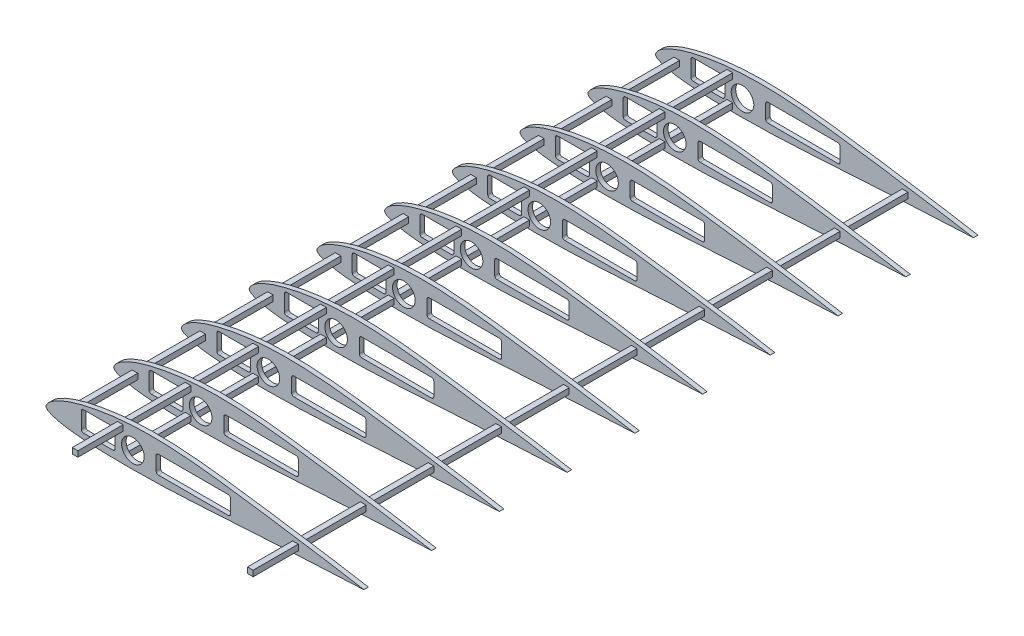
SolidWorks part; units mm, degrees
ref_plane "Front Plane" through (0, 0, 0) normal (0, 0, 1) x (1, 0, 0)
ref_plane "Top Plane" through (0, 0, 0) normal (0, 1, 0) x (1, 0, 0)
ref_plane "Right Plane" through (0, 0, 0) normal (1, 0, 0) x (0, 0, -1)
curve "Curve1"
  spline degree 3 poles (25.2088, 0.0031, 0) (25.4484, -0.0031, 0) (25.2117, 0.0209, 0) (25.0251, 0.0571, 0) (24.5852, 0.1328, 0) (24.06, 0.2322, 0) (23.3873, 0.3478, 0) (22.6018, 0.4739, 0) (21.7032, 0.6151, 0) (20.7068, 0.7694, 0) (19.6256, 0.9351, 0) (18.475, 1.1087, 0) (17.2708, 1.2865, 0) (16.0292, 1.4651, 0) (14.7666, 1.6379, 0) (13.5001, 1.8004, 0) (12.2446, 1.9439, 0) (11.0116, 2.0561, 0) (9.8099, 2.1301, 0) (8.6464, 2.1619, 0) (7.5276, 2.1493, 0) (6.459, 2.093, 0) (5.4467, 1.9949, 0) (4.4976, 1.8641, 0) (3.6202, 1.7053, 0) (2.8233, 1.523, 0) (2.1144, 1.3219, 0) (1.5008, 1.1059, 0) (0.9865, 0.8803, 0) (0.5779, 0.652, 0) (0.2708, 0.4245, 0) (0.0836, 0.2161, 0) (-0.0349, 0.004, 0) (0.089, -0.2027, 0) (0.3409, -0.3252, 0) (0.701, -0.4662, 0) (1.1913, -0.581, 0) (1.8002, -0.6841, 0) (2.5267, -0.768, 0) (3.3632, -0.8336, 0) (4.3022, -0.8807, 0) (5.334, -0.9092, 0) (6.4474, -0.9203, 0) (7.6302, -0.9134, 0) (8.8703, -0.8889, 0) (10.1572, -0.841, 0) (11.4808, -0.7741, 0) (12.8288, -0.6974, 0) (14.1854, -0.6164, 0) (15.5332, -0.5343, 0) (16.8545, -0.4545, 0) (18.1325, -0.3787, 0) (19.3501, -0.3089, 0) (20.4916, -0.2458, 0) (21.5411, -0.1904, 0) (22.4855, -0.1429, 0) (23.3092, -0.1017, 0) (24.0133, -0.0644, 0) (24.5612, -0.0287, 0) (25.0167, -0.0091, 0) (25.2088, 0.0031, 0) (25.4484, -0.0031, 0) (25.2117, 0.0209, 0) knots -0.015092 -0.006889 -0.001754 0 0.001748 0.006827 0.01488 0.025572 0.038694 0.054171 0.071834 0.091435 0.112685 0.135293 0.158944 0.183315 0.20807 0.232879 0.257399 0.281384 0.304706 0.327241 0.348897 0.369607 0.389308 0.407886 0.425177 0.441027 0.4553 0.467904 0.478752 0.487814 0.49509 0.500617 0.504451 0.507804 0.513091 0.520546 0.530249 0.542214 0.556382 0.572656 0.590895 0.610925 0.632536 0.655496 0.679547 0.704499 0.730211 0.756436 0.782837 0.809062 0.834776 0.859641 0.883338 0.905541 0.925965 0.944326 0.960366 0.973929 0.984908 0.993111 0.998246 1 1.001748 1.006827 1.01488 periodic
sketch "Sketch1" plane through (0, 0, 0) normal (0, 0, 1) x (1, 0, 0)
  line L0 (357.6496, 0) -> (0, 0) construction
  line L1 (0, 0) -> (0, 5.0209) construction
  spline S1 degree 3 poles (354.9573, 0.0431) (358.3317, -0.0432) (354.9981, 0.2938) (352.3707, 0.8024) (346.1763, 1.8676) (338.7813, 3.2655) (329.3081, 4.8919) (318.2482, 6.6648) (305.5952, 8.6507) (291.564, 10.8193) (276.34, 13.1505) (260.1392, 15.5903) (243.1815, 18.0913) (225.699, 20.6027) (207.9209, 23.0318) (190.087, 25.3152) (172.4086, 27.3328) (155.0467, 28.9096) (138.1258, 29.947) (121.7437, 30.3922) (105.9899, 30.2108) (90.9433, 29.4155) (76.6903, 28.0308) (63.3272, 26.1868) (50.9728, 23.9485) (39.7523, 21.3791) (29.7714, 18.545) (21.1318, 15.5018) (13.8914, 12.3237) (8.1391, 9.1075) (3.8158, 5.9031) (1.1802, 2.9693) (-0.4877, -0.018) (1.2572, -2.9285) (4.805, -4.6528) (9.8754, -6.6365) (16.78, -8.2511) (25.3535, -9.7017) (35.5828, -10.8813) (47.3622, -11.8027) (60.5842, -12.4624) (75.1117, -12.8607) (90.7897, -13.0132) (107.4435, -12.9137) (124.9052, -12.5651) (143.0256, -11.8868) (161.6617, -10.9405) (180.6424, -9.8572) (199.7442, -8.7119) (218.721, -7.5525) (237.3263, -6.4253) (255.3201, -5.3536) (272.4652, -4.367) (288.5372, -3.4753) (303.3148, -2.6922) (316.6121, -2.0207) (328.2104, -1.4385) (338.1246, -0.9102) (345.8395, -0.4061) (352.2525, -0.129) (354.9573, 0.0431) (358.3317, -0.0432) (354.9981, 0.2938) knots -0.015092 -0.006889 -0.001754 0 0.001748 0.006827 0.01488 0.025572 0.038694 0.054171 0.071834 0.091435 0.112685 0.135293 0.158944 0.183315 0.20807 0.232879 0.257399 0.281384 0.304706 0.327241 0.348897 0.369607 0.389308 0.407886 0.425177 0.441027 0.4553 0.467904 0.478752 0.487814 0.49509 0.500617 0.504451 0.507804 0.513091 0.520546 0.530249 0.542214 0.556382 0.572656 0.590895 0.610925 0.632536 0.655496 0.679547 0.704499 0.730211 0.756436 0.782837 0.809062 0.834776 0.859641 0.883338 0.905541 0.925965 0.944326 0.960366 0.973929 0.984908 0.993111 0.998246 1 1.001748 1.006827 1.01488 only from (357.6496, 0) to (357.6496, 0)
  dimension "D1" = 357.6496
ref_plane "Plane3" through (0, 0, 76.2) normal (0, 0, 1) x (1, 0, 0)
ref_plane "Plane4" through (0, 0, 152.4) normal (0, 0, 1) x (1, 0, 0)
ref_plane "Plane5" through (0, 0, 228.6) normal (0, 0, 1) x (1, 0, 0)
ref_plane "Plane6" through (0, 0, 304.8) normal (0, 0, 1) x (1, 0, 0)
ref_plane "Plane7" through (0, 0, 381) normal (0, 0, 1) x (1, 0, 0)
ref_plane "Plane8" through (0, 0, 457.2) normal (0, 0, 1) x (1, 0, 0)
ref_plane "Plane9" through (0, 0, 533.4) normal (0, 0, 1) x (1, 0, 0)
ref_plane "Plane10" through (0, 0, 609.6) normal (0, 0, 1) x (1, 0, 0)
ref_plane "Plane11" through (0, 0, 685.8) normal (0, 0, 1) x (1, 0, 0)
sketch "Sketch5" plane through (0, 0, 76.2) normal (0, 0, 1) x (1, 0, 0)
  spline S0 degree 3 poles (354.9573, 0.0431) (358.3317, -0.0432) (354.9981, 0.2938) (352.3707, 0.8024) (346.1763, 1.8676) (338.7813, 3.2655) (329.3081, 4.8919) (318.2482, 6.6648) (305.5952, 8.6507) (291.564, 10.8193) (276.34, 13.1505) (260.1392, 15.5903) (243.1815, 18.0913) (225.699, 20.6027) (207.9209, 23.0318) (190.087, 25.3152) (172.4086, 27.3328) (155.0467, 28.9096) (138.1258, 29.947) (121.7437, 30.3922) (105.9899, 30.2108) (90.9433, 29.4155) (76.6903, 28.0308) (63.3272, 26.1868) (50.9728, 23.9485) (39.7523, 21.3791) (29.7714, 18.545) (21.1318, 15.5018) (13.8914, 12.3237) (8.1391, 9.1075) (3.8158, 5.9031) (1.1802, 2.9693) (-0.4877, -0.018) (1.2572, -2.9285) (4.805, -4.6528) (9.8754, -6.6365) (16.78, -8.2511) (25.3535, -9.7017) (35.5828, -10.8813) (47.3622, -11.8027) (60.5842, -12.4624) (75.1117, -12.8607) (90.7897, -13.0132) (107.4435, -12.9137) (124.9052, -12.5651) (143.0256, -11.8868) (161.6617, -10.9405) (180.6424, -9.8572) (199.7442, -8.7119) (218.721, -7.5525) (237.3263, -6.4253) (255.3201, -5.3536) (272.4652, -4.367) (288.5372, -3.4753) (303.3148, -2.6922) (316.6121, -2.0207) (328.2104, -1.4385) (338.1246, -0.9102) (345.8395, -0.4061) (352.2525, -0.129) (354.9573, 0.0431) (358.3317, -0.0432) (354.9981, 0.2938) knots -0.015092 -0.006889 -0.001754 0 0.001748 0.006827 0.01488 0.025572 0.038694 0.054171 0.071834 0.091435 0.112685 0.135293 0.158944 0.183315 0.20807 0.232879 0.257399 0.281384 0.304706 0.327241 0.348897 0.369607 0.389308 0.407886 0.425177 0.441027 0.4553 0.467904 0.478752 0.487814 0.49509 0.500617 0.504451 0.507804 0.513091 0.520546 0.530249 0.542214 0.556382 0.572656 0.590895 0.610925 0.632536 0.655496 0.679547 0.704499 0.730211 0.756436 0.782837 0.809062 0.834776 0.859641 0.883338 0.905541 0.925965 0.944326 0.960366 0.973929 0.984908 0.993111 0.998246 1 1.001748 1.006827 1.01488 only from (357.6496, 0) to (357.6496, 0) construction
  spline S1 degree 3 poles (354.9573, 0.0431) (358.3317, -0.0432) (354.9981, 0.2938) (352.3707, 0.8024) (346.1763, 1.8676) (338.7813, 3.2655) (329.3081, 4.8919) (318.2482, 6.6648) (305.5952, 8.6507) (291.564, 10.8193) (276.34, 13.1505) (260.1392, 15.5903) (243.1815, 18.0913) (225.699, 20.6027) (207.9209, 23.0318) (190.087, 25.3152) (172.4086, 27.3328) (155.0467, 28.9096) (138.1258, 29.947) (121.7437, 30.3922) (105.9899, 30.2108) (90.9433, 29.4155) (76.6903, 28.0308) (63.3272, 26.1868) (50.9728, 23.9485) (39.7523, 21.3791) (29.7714, 18.545) (21.1318, 15.5018) (13.8914, 12.3237) (8.1391, 9.1075) (3.8158, 5.9031) (1.1802, 2.9693) (-0.4877, -0.018) (1.2572, -2.9285) (4.805, -4.6528) (9.8754, -6.6365) (16.78, -8.2511) (25.3535, -9.7017) (35.5828, -10.8813) (47.3622, -11.8027) (60.5842, -12.4624) (75.1117, -12.8607) (90.7897, -13.0132) (107.4435, -12.9137) (124.9052, -12.5651) (143.0256, -11.8868) (161.6617, -10.9405) (180.6424, -9.8572) (199.7442, -8.7119) (218.721, -7.5525) (237.3263, -6.4253) (255.3201, -5.3536) (272.4652, -4.367) (288.5372, -3.4753) (303.3148, -2.6922) (316.6121, -2.0207) (328.2104, -1.4385) (338.1246, -0.9102) (345.8395, -0.4061) (352.2525, -0.129) (354.9573, 0.0431) (358.3317, -0.0432) (354.9981, 0.2938) knots -0.015092 -0.006889 -0.001754 0 0.001748 0.006827 0.01488 0.025572 0.038694 0.054171 0.071834 0.091435 0.112685 0.135293 0.158944 0.183315 0.20807 0.232879 0.257399 0.281384 0.304706 0.327241 0.348897 0.369607 0.389308 0.407886 0.425177 0.441027 0.4553 0.467904 0.478752 0.487814 0.49509 0.500617 0.504451 0.507804 0.513091 0.520546 0.530249 0.542214 0.556382 0.572656 0.590895 0.610925 0.632536 0.655496 0.679547 0.704499 0.730211 0.756436 0.782837 0.809062 0.834776 0.859641 0.883338 0.905541 0.925965 0.944326 0.960366 0.973929 0.984908 0.993111 0.998246 1 1.001748 1.006827 1.01488 only from (357.6496, 0) to (357.6496, 0)
sketch "Sketch6" plane through (0, 0, 152.4) normal (0, 0, 1) x (1, 0, 0)
  spline S0 degree 3 poles (354.9573, 0.0431) (358.3317, -0.0432) (354.9981, 0.2938) (352.3707, 0.8024) (346.1763, 1.8676) (338.7813, 3.2655) (329.3081, 4.8919) (318.2482, 6.6648) (305.5952, 8.6507) (291.564, 10.8193) (276.34, 13.1505) (260.1392, 15.5903) (243.1815, 18.0913) (225.699, 20.6027) (207.9209, 23.0318) (190.087, 25.3152) (172.4086, 27.3328) (155.0467, 28.9096) (138.1258, 29.947) (121.7437, 30.3922) (105.9899, 30.2108) (90.9433, 29.4155) (76.6903, 28.0308) (63.3272, 26.1868) (50.9728, 23.9485) (39.7523, 21.3791) (29.7714, 18.545) (21.1318, 15.5018) (13.8914, 12.3237) (8.1391, 9.1075) (3.8158, 5.9031) (1.1802, 2.9693) (-0.4877, -0.018) (1.2572, -2.9285) (4.805, -4.6528) (9.8754, -6.6365) (16.78, -8.2511) (25.3535, -9.7017) (35.5828, -10.8813) (47.3622, -11.8027) (60.5842, -12.4624) (75.1117, -12.8607) (90.7897, -13.0132) (107.4435, -12.9137) (124.9052, -12.5651) (143.0256, -11.8868) (161.6617, -10.9405) (180.6424, -9.8572) (199.7442, -8.7119) (218.721, -7.5525) (237.3263, -6.4253) (255.3201, -5.3536) (272.4652, -4.367) (288.5372, -3.4753) (303.3148, -2.6922) (316.6121, -2.0207) (328.2104, -1.4385) (338.1246, -0.9102) (345.8395, -0.4061) (352.2525, -0.129) (354.9573, 0.0431) (358.3317, -0.0432) (354.9981, 0.2938) knots -0.015092 -0.006889 -0.001754 0 0.001748 0.006827 0.01488 0.025572 0.038694 0.054171 0.071834 0.091435 0.112685 0.135293 0.158944 0.183315 0.20807 0.232879 0.257399 0.281384 0.304706 0.327241 0.348897 0.369607 0.389308 0.407886 0.425177 0.441027 0.4553 0.467904 0.478752 0.487814 0.49509 0.500617 0.504451 0.507804 0.513091 0.520546 0.530249 0.542214 0.556382 0.572656 0.590895 0.610925 0.632536 0.655496 0.679547 0.704499 0.730211 0.756436 0.782837 0.809062 0.834776 0.859641 0.883338 0.905541 0.925965 0.944326 0.960366 0.973929 0.984908 0.993111 0.998246 1 1.001748 1.006827 1.01488 only from (357.6496, 0) to (357.6496, 0) construction
  spline S1 degree 3 poles (354.9573, 0.0431) (358.3317, -0.0432) (354.9981, 0.2938) (352.3707, 0.8024) (346.1763, 1.8676) (338.7813, 3.2655) (329.3081, 4.8919) (318.2482, 6.6648) (305.5952, 8.6507) (291.564, 10.8193) (276.34, 13.1505) (260.1392, 15.5903) (243.1815, 18.0913) (225.699, 20.6027) (207.9209, 23.0318) (190.087, 25.3152) (172.4086, 27.3328) (155.0467, 28.9096) (138.1258, 29.947) (121.7437, 30.3922) (105.9899, 30.2108) (90.9433, 29.4155) (76.6903, 28.0308) (63.3272, 26.1868) (50.9728, 23.9485) (39.7523, 21.3791) (29.7714, 18.545) (21.1318, 15.5018) (13.8914, 12.3237) (8.1391, 9.1075) (3.8158, 5.9031) (1.1802, 2.9693) (-0.4877, -0.018) (1.2572, -2.9285) (4.805, -4.6528) (9.8754, -6.6365) (16.78, -8.2511) (25.3535, -9.7017) (35.5828, -10.8813) (47.3622, -11.8027) (60.5842, -12.4624) (75.1117, -12.8607) (90.7897, -13.0132) (107.4435, -12.9137) (124.9052, -12.5651) (143.0256, -11.8868) (161.6617, -10.9405) (180.6424, -9.8572) (199.7442, -8.7119) (218.721, -7.5525) (237.3263, -6.4253) (255.3201, -5.3536) (272.4652, -4.367) (288.5372, -3.4753) (303.3148, -2.6922) (316.6121, -2.0207) (328.2104, -1.4385) (338.1246, -0.9102) (345.8395, -0.4061) (352.2525, -0.129) (354.9573, 0.0431) (358.3317, -0.0432) (354.9981, 0.2938) knots -0.015092 -0.006889 -0.001754 0 0.001748 0.006827 0.01488 0.025572 0.038694 0.054171 0.071834 0.091435 0.112685 0.135293 0.158944 0.183315 0.20807 0.232879 0.257399 0.281384 0.304706 0.327241 0.348897 0.369607 0.389308 0.407886 0.425177 0.441027 0.4553 0.467904 0.478752 0.487814 0.49509 0.500617 0.504451 0.507804 0.513091 0.520546 0.530249 0.542214 0.556382 0.572656 0.590895 0.610925 0.632536 0.655496 0.679547 0.704499 0.730211 0.756436 0.782837 0.809062 0.834776 0.859641 0.883338 0.905541 0.925965 0.944326 0.960366 0.973929 0.984908 0.993111 0.998246 1 1.001748 1.006827 1.01488 only from (357.6496, 0) to (357.6496, 0)
sketch "Sketch7" plane through (0, 0, 228.6) normal (0, 0, 1) x (1, 0, 0)
  spline S0 degree 3 poles (354.9573, 0.0431) (358.3317, -0.0432) (354.9981, 0.2938) (352.3707, 0.8024) (346.1763, 1.8676) (338.7813, 3.2655) (329.3081, 4.8919) (318.2482, 6.6648) (305.5952, 8.6507) (291.564, 10.8193) (276.34, 13.1505) (260.1392, 15.5903) (243.1815, 18.0913) (225.699, 20.6027) (207.9209, 23.0318) (190.087, 25.3152) (172.4086, 27.3328) (155.0467, 28.9096) (138.1258, 29.947) (121.7437, 30.3922) (105.9899, 30.2108) (90.9433, 29.4155) (76.6903, 28.0308) (63.3272, 26.1868) (50.9728, 23.9485) (39.7523, 21.3791) (29.7714, 18.545) (21.1318, 15.5018) (13.8914, 12.3237) (8.1391, 9.1075) (3.8158, 5.9031) (1.1802, 2.9693) (-0.4877, -0.018) (1.2572, -2.9285) (4.805, -4.6528) (9.8754, -6.6365) (16.78, -8.2511) (25.3535, -9.7017) (35.5828, -10.8813) (47.3622, -11.8027) (60.5842, -12.4624) (75.1117, -12.8607) (90.7897, -13.0132) (107.4435, -12.9137) (124.9052, -12.5651) (143.0256, -11.8868) (161.6617, -10.9405) (180.6424, -9.8572) (199.7442, -8.7119) (218.721, -7.5525) (237.3263, -6.4253) (255.3201, -5.3536) (272.4652, -4.367) (288.5372, -3.4753) (303.3148, -2.6922) (316.6121, -2.0207) (328.2104, -1.4385) (338.1246, -0.9102) (345.8395, -0.4061) (352.2525, -0.129) (354.9573, 0.0431) (358.3317, -0.0432) (354.9981, 0.2938) knots -0.015092 -0.006889 -0.001754 0 0.001748 0.006827 0.01488 0.025572 0.038694 0.054171 0.071834 0.091435 0.112685 0.135293 0.158944 0.183315 0.20807 0.232879 0.257399 0.281384 0.304706 0.327241 0.348897 0.369607 0.389308 0.407886 0.425177 0.441027 0.4553 0.467904 0.478752 0.487814 0.49509 0.500617 0.504451 0.507804 0.513091 0.520546 0.530249 0.542214 0.556382 0.572656 0.590895 0.610925 0.632536 0.655496 0.679547 0.704499 0.730211 0.756436 0.782837 0.809062 0.834776 0.859641 0.883338 0.905541 0.925965 0.944326 0.960366 0.973929 0.984908 0.993111 0.998246 1 1.001748 1.006827 1.01488 only from (357.6496, 0) to (357.6496, 0) construction
  spline S1 degree 3 poles (354.9573, 0.0431) (358.3317, -0.0432) (354.9981, 0.2938) (352.3707, 0.8024) (346.1763, 1.8676) (338.7813, 3.2655) (329.3081, 4.8919) (318.2482, 6.6648) (305.5952, 8.6507) (291.564, 10.8193) (276.34, 13.1505) (260.1392, 15.5903) (243.1815, 18.0913) (225.699, 20.6027) (207.9209, 23.0318) (190.087, 25.3152) (172.4086, 27.3328) (155.0467, 28.9096) (138.1258, 29.947) (121.7437, 30.3922) (105.9899, 30.2108) (90.9433, 29.4155) (76.6903, 28.0308) (63.3272, 26.1868) (50.9728, 23.9485) (39.7523, 21.3791) (29.7714, 18.545) (21.1318, 15.5018) (13.8914, 12.3237) (8.1391, 9.1075) (3.8158, 5.9031) (1.1802, 2.9693) (-0.4877, -0.018) (1.2572, -2.9285) (4.805, -4.6528) (9.8754, -6.6365) (16.78, -8.2511) (25.3535, -9.7017) (35.5828, -10.8813) (47.3622, -11.8027) (60.5842, -12.4624) (75.1117, -12.8607) (90.7897, -13.0132) (107.4435, -12.9137) (124.9052, -12.5651) (143.0256, -11.8868) (161.6617, -10.9405) (180.6424, -9.8572) (199.7442, -8.7119) (218.721, -7.5525) (237.3263, -6.4253) (255.3201, -5.3536) (272.4652, -4.367) (288.5372, -3.4753) (303.3148, -2.6922) (316.6121, -2.0207) (328.2104, -1.4385) (338.1246, -0.9102) (345.8395, -0.4061) (352.2525, -0.129) (354.9573, 0.0431) (358.3317, -0.0432) (354.9981, 0.2938) knots -0.015092 -0.006889 -0.001754 0 0.001748 0.006827 0.01488 0.025572 0.038694 0.054171 0.071834 0.091435 0.112685 0.135293 0.158944 0.183315 0.20807 0.232879 0.257399 0.281384 0.304706 0.327241 0.348897 0.369607 0.389308 0.407886 0.425177 0.441027 0.4553 0.467904 0.478752 0.487814 0.49509 0.500617 0.504451 0.507804 0.513091 0.520546 0.530249 0.542214 0.556382 0.572656 0.590895 0.610925 0.632536 0.655496 0.679547 0.704499 0.730211 0.756436 0.782837 0.809062 0.834776 0.859641 0.883338 0.905541 0.925965 0.944326 0.960366 0.973929 0.984908 0.993111 0.998246 1 1.001748 1.006827 1.01488 only from (357.6496, 0) to (357.6496, 0)
sketch "Sketch8" plane through (0, 0, 304.8) normal (0, 0, 1) x (1, 0, 0)
  spline S0 degree 3 poles (354.9573, 0.0431) (358.3317, -0.0432) (354.9981, 0.2938) (352.3707, 0.8024) (346.1763, 1.8676) (338.7813, 3.2655) (329.3081, 4.8919) (318.2482, 6.6648) (305.5952, 8.6507) (291.564, 10.8193) (276.34, 13.1505) (260.1392, 15.5903) (243.1815, 18.0913) (225.699, 20.6027) (207.9209, 23.0318) (190.087, 25.3152) (172.4086, 27.3328) (155.0467, 28.9096) (138.1258, 29.947) (121.7437, 30.3922) (105.9899, 30.2108) (90.9433, 29.4155) (76.6903, 28.0308) (63.3272, 26.1868) (50.9728, 23.9485) (39.7523, 21.3791) (29.7714, 18.545) (21.1318, 15.5018) (13.8914, 12.3237) (8.1391, 9.1075) (3.8158, 5.9031) (1.1802, 2.9693) (-0.4877, -0.018) (1.2572, -2.9285) (4.805, -4.6528) (9.8754, -6.6365) (16.78, -8.2511) (25.3535, -9.7017) (35.5828, -10.8813) (47.3622, -11.8027) (60.5842, -12.4624) (75.1117, -12.8607) (90.7897, -13.0132) (107.4435, -12.9137) (124.9052, -12.5651) (143.0256, -11.8868) (161.6617, -10.9405) (180.6424, -9.8572) (199.7442, -8.7119) (218.721, -7.5525) (237.3263, -6.4253) (255.3201, -5.3536) (272.4652, -4.367) (288.5372, -3.4753) (303.3148, -2.6922) (316.6121, -2.0207) (328.2104, -1.4385) (338.1246, -0.9102) (345.8395, -0.4061) (352.2525, -0.129) (354.9573, 0.0431) (358.3317, -0.0432) (354.9981, 0.2938) knots -0.015092 -0.006889 -0.001754 0 0.001748 0.006827 0.01488 0.025572 0.038694 0.054171 0.071834 0.091435 0.112685 0.135293 0.158944 0.183315 0.20807 0.232879 0.257399 0.281384 0.304706 0.327241 0.348897 0.369607 0.389308 0.407886 0.425177 0.441027 0.4553 0.467904 0.478752 0.487814 0.49509 0.500617 0.504451 0.507804 0.513091 0.520546 0.530249 0.542214 0.556382 0.572656 0.590895 0.610925 0.632536 0.655496 0.679547 0.704499 0.730211 0.756436 0.782837 0.809062 0.834776 0.859641 0.883338 0.905541 0.925965 0.944326 0.960366 0.973929 0.984908 0.993111 0.998246 1 1.001748 1.006827 1.01488 only from (357.6496, 0) to (357.6496, 0) construction
  spline S1 degree 3 poles (354.9573, 0.0431) (358.3317, -0.0432) (354.9981, 0.2938) (352.3707, 0.8024) (346.1763, 1.8676) (338.7813, 3.2655) (329.3081, 4.8919) (318.2482, 6.6648) (305.5952, 8.6507) (291.564, 10.8193) (276.34, 13.1505) (260.1392, 15.5903) (243.1815, 18.0913) (225.699, 20.6027) (207.9209, 23.0318) (190.087, 25.3152) (172.4086, 27.3328) (155.0467, 28.9096) (138.1258, 29.947) (121.7437, 30.3922) (105.9899, 30.2108) (90.9433, 29.4155) (76.6903, 28.0308) (63.3272, 26.1868) (50.9728, 23.9485) (39.7523, 21.3791) (29.7714, 18.545) (21.1318, 15.5018) (13.8914, 12.3237) (8.1391, 9.1075) (3.8158, 5.9031) (1.1802, 2.9693) (-0.4877, -0.018) (1.2572, -2.9285) (4.805, -4.6528) (9.8754, -6.6365) (16.78, -8.2511) (25.3535, -9.7017) (35.5828, -10.8813) (47.3622, -11.8027) (60.5842, -12.4624) (75.1117, -12.8607) (90.7897, -13.0132) (107.4435, -12.9137) (124.9052, -12.5651) (143.0256, -11.8868) (161.6617, -10.9405) (180.6424, -9.8572) (199.7442, -8.7119) (218.721, -7.5525) (237.3263, -6.4253) (255.3201, -5.3536) (272.4652, -4.367) (288.5372, -3.4753) (303.3148, -2.6922) (316.6121, -2.0207) (328.2104, -1.4385) (338.1246, -0.9102) (345.8395, -0.4061) (352.2525, -0.129) (354.9573, 0.0431) (358.3317, -0.0432) (354.9981, 0.2938) knots -0.015092 -0.006889 -0.001754 0 0.001748 0.006827 0.01488 0.025572 0.038694 0.054171 0.071834 0.091435 0.112685 0.135293 0.158944 0.183315 0.20807 0.232879 0.257399 0.281384 0.304706 0.327241 0.348897 0.369607 0.389308 0.407886 0.425177 0.441027 0.4553 0.467904 0.478752 0.487814 0.49509 0.500617 0.504451 0.507804 0.513091 0.520546 0.530249 0.542214 0.556382 0.572656 0.590895 0.610925 0.632536 0.655496 0.679547 0.704499 0.730211 0.756436 0.782837 0.809062 0.834776 0.859641 0.883338 0.905541 0.925965 0.944326 0.960366 0.973929 0.984908 0.993111 0.998246 1 1.001748 1.006827 1.01488 only from (357.6496, 0) to (357.6496, 0)
sketch "Sketch9" plane through (0, 0, 381) normal (0, 0, 1) x (1, 0, 0)
  spline S0 degree 3 poles (354.9573, 0.0431) (358.3317, -0.0432) (354.9981, 0.2938) (352.3707, 0.8024) (346.1763, 1.8676) (338.7813, 3.2655) (329.3081, 4.8919) (318.2482, 6.6648) (305.5952, 8.6507) (291.564, 10.8193) (276.34, 13.1505) (260.1392, 15.5903) (243.1815, 18.0913) (225.699, 20.6027) (207.9209, 23.0318) (190.087, 25.3152) (172.4086, 27.3328) (155.0467, 28.9096) (138.1258, 29.947) (121.7437, 30.3922) (105.9899, 30.2108) (90.9433, 29.4155) (76.6903, 28.0308) (63.3272, 26.1868) (50.9728, 23.9485) (39.7523, 21.3791) (29.7714, 18.545) (21.1318, 15.5018) (13.8914, 12.3237) (8.1391, 9.1075) (3.8158, 5.9031) (1.1802, 2.9693) (-0.4877, -0.018) (1.2572, -2.9285) (4.805, -4.6528) (9.8754, -6.6365) (16.78, -8.2511) (25.3535, -9.7017) (35.5828, -10.8813) (47.3622, -11.8027) (60.5842, -12.4624) (75.1117, -12.8607) (90.7897, -13.0132) (107.4435, -12.9137) (124.9052, -12.5651) (143.0256, -11.8868) (161.6617, -10.9405) (180.6424, -9.8572) (199.7442, -8.7119) (218.721, -7.5525) (237.3263, -6.4253) (255.3201, -5.3536) (272.4652, -4.367) (288.5372, -3.4753) (303.3148, -2.6922) (316.6121, -2.0207) (328.2104, -1.4385) (338.1246, -0.9102) (345.8395, -0.4061) (352.2525, -0.129) (354.9573, 0.0431) (358.3317, -0.0432) (354.9981, 0.2938) knots -0.015092 -0.006889 -0.001754 0 0.001748 0.006827 0.01488 0.025572 0.038694 0.054171 0.071834 0.091435 0.112685 0.135293 0.158944 0.183315 0.20807 0.232879 0.257399 0.281384 0.304706 0.327241 0.348897 0.369607 0.389308 0.407886 0.425177 0.441027 0.4553 0.467904 0.478752 0.487814 0.49509 0.500617 0.504451 0.507804 0.513091 0.520546 0.530249 0.542214 0.556382 0.572656 0.590895 0.610925 0.632536 0.655496 0.679547 0.704499 0.730211 0.756436 0.782837 0.809062 0.834776 0.859641 0.883338 0.905541 0.925965 0.944326 0.960366 0.973929 0.984908 0.993111 0.998246 1 1.001748 1.006827 1.01488 only from (357.6496, 0) to (357.6496, 0) construction
  spline S1 degree 3 poles (354.9573, 0.0431) (358.3317, -0.0432) (354.9981, 0.2938) (352.3707, 0.8024) (346.1763, 1.8676) (338.7813, 3.2655) (329.3081, 4.8919) (318.2482, 6.6648) (305.5952, 8.6507) (291.564, 10.8193) (276.34, 13.1505) (260.1392, 15.5903) (243.1815, 18.0913) (225.699, 20.6027) (207.9209, 23.0318) (190.087, 25.3152) (172.4086, 27.3328) (155.0467, 28.9096) (138.1258, 29.947) (121.7437, 30.3922) (105.9899, 30.2108) (90.9433, 29.4155) (76.6903, 28.0308) (63.3272, 26.1868) (50.9728, 23.9485) (39.7523, 21.3791) (29.7714, 18.545) (21.1318, 15.5018) (13.8914, 12.3237) (8.1391, 9.1075) (3.8158, 5.9031) (1.1802, 2.9693) (-0.4877, -0.018) (1.2572, -2.9285) (4.805, -4.6528) (9.8754, -6.6365) (16.78, -8.2511) (25.3535, -9.7017) (35.5828, -10.8813) (47.3622, -11.8027) (60.5842, -12.4624) (75.1117, -12.8607) (90.7897, -13.0132) (107.4435, -12.9137) (124.9052, -12.5651) (143.0256, -11.8868) (161.6617, -10.9405) (180.6424, -9.8572) (199.7442, -8.7119) (218.721, -7.5525) (237.3263, -6.4253) (255.3201, -5.3536) (272.4652, -4.367) (288.5372, -3.4753) (303.3148, -2.6922) (316.6121, -2.0207) (328.2104, -1.4385) (338.1246, -0.9102) (345.8395, -0.4061) (352.2525, -0.129) (354.9573, 0.0431) (358.3317, -0.0432) (354.9981, 0.2938) knots -0.015092 -0.006889 -0.001754 0 0.001748 0.006827 0.01488 0.025572 0.038694 0.054171 0.071834 0.091435 0.112685 0.135293 0.158944 0.183315 0.20807 0.232879 0.257399 0.281384 0.304706 0.327241 0.348897 0.369607 0.389308 0.407886 0.425177 0.441027 0.4553 0.467904 0.478752 0.487814 0.49509 0.500617 0.504451 0.507804 0.513091 0.520546 0.530249 0.542214 0.556382 0.572656 0.590895 0.610925 0.632536 0.655496 0.679547 0.704499 0.730211 0.756436 0.782837 0.809062 0.834776 0.859641 0.883338 0.905541 0.925965 0.944326 0.960366 0.973929 0.984908 0.993111 0.998246 1 1.001748 1.006827 1.01488 only from (357.6496, 0) to (357.6496, 0)
sketch "Sketch10" plane through (0, 0, 457.2) normal (0, 0, 1) x (1, 0, 0)
  spline S0 degree 3 poles (354.9573, 0.0431) (358.3317, -0.0432) (354.9981, 0.2938) (352.3707, 0.8024) (346.1763, 1.8676) (338.7813, 3.2655) (329.3081, 4.8919) (318.2482, 6.6648) (305.5952, 8.6507) (291.564, 10.8193) (276.34, 13.1505) (260.1392, 15.5903) (243.1815, 18.0913) (225.699, 20.6027) (207.9209, 23.0318) (190.087, 25.3152) (172.4086, 27.3328) (155.0467, 28.9096) (138.1258, 29.947) (121.7437, 30.3922) (105.9899, 30.2108) (90.9433, 29.4155) (76.6903, 28.0308) (63.3272, 26.1868) (50.9728, 23.9485) (39.7523, 21.3791) (29.7714, 18.545) (21.1318, 15.5018) (13.8914, 12.3237) (8.1391, 9.1075) (3.8158, 5.9031) (1.1802, 2.9693) (-0.4877, -0.018) (1.2572, -2.9285) (4.805, -4.6528) (9.8754, -6.6365) (16.78, -8.2511) (25.3535, -9.7017) (35.5828, -10.8813) (47.3622, -11.8027) (60.5842, -12.4624) (75.1117, -12.8607) (90.7897, -13.0132) (107.4435, -12.9137) (124.9052, -12.5651) (143.0256, -11.8868) (161.6617, -10.9405) (180.6424, -9.8572) (199.7442, -8.7119) (218.721, -7.5525) (237.3263, -6.4253) (255.3201, -5.3536) (272.4652, -4.367) (288.5372, -3.4753) (303.3148, -2.6922) (316.6121, -2.0207) (328.2104, -1.4385) (338.1246, -0.9102) (345.8395, -0.4061) (352.2525, -0.129) (354.9573, 0.0431) (358.3317, -0.0432) (354.9981, 0.2938) knots -0.015092 -0.006889 -0.001754 0 0.001748 0.006827 0.01488 0.025572 0.038694 0.054171 0.071834 0.091435 0.112685 0.135293 0.158944 0.183315 0.20807 0.232879 0.257399 0.281384 0.304706 0.327241 0.348897 0.369607 0.389308 0.407886 0.425177 0.441027 0.4553 0.467904 0.478752 0.487814 0.49509 0.500617 0.504451 0.507804 0.513091 0.520546 0.530249 0.542214 0.556382 0.572656 0.590895 0.610925 0.632536 0.655496 0.679547 0.704499 0.730211 0.756436 0.782837 0.809062 0.834776 0.859641 0.883338 0.905541 0.925965 0.944326 0.960366 0.973929 0.984908 0.993111 0.998246 1 1.001748 1.006827 1.01488 only from (357.6496, 0) to (357.6496, 0) construction
  spline S1 degree 3 poles (354.9573, 0.0431) (358.3317, -0.0432) (354.9981, 0.2938) (352.3707, 0.8024) (346.1763, 1.8676) (338.7813, 3.2655) (329.3081, 4.8919) (318.2482, 6.6648) (305.5952, 8.6507) (291.564, 10.8193) (276.34, 13.1505) (260.1392, 15.5903) (243.1815, 18.0913) (225.699, 20.6027) (207.9209, 23.0318) (190.087, 25.3152) (172.4086, 27.3328) (155.0467, 28.9096) (138.1258, 29.947) (121.7437, 30.3922) (105.9899, 30.2108) (90.9433, 29.4155) (76.6903, 28.0308) (63.3272, 26.1868) (50.9728, 23.9485) (39.7523, 21.3791) (29.7714, 18.545) (21.1318, 15.5018) (13.8914, 12.3237) (8.1391, 9.1075) (3.8158, 5.9031) (1.1802, 2.9693) (-0.4877, -0.018) (1.2572, -2.9285) (4.805, -4.6528) (9.8754, -6.6365) (16.78, -8.2511) (25.3535, -9.7017) (35.5828, -10.8813) (47.3622, -11.8027) (60.5842, -12.4624) (75.1117, -12.8607) (90.7897, -13.0132) (107.4435, -12.9137) (124.9052, -12.5651) (143.0256, -11.8868) (161.6617, -10.9405) (180.6424, -9.8572) (199.7442, -8.7119) (218.721, -7.5525) (237.3263, -6.4253) (255.3201, -5.3536) (272.4652, -4.367) (288.5372, -3.4753) (303.3148, -2.6922) (316.6121, -2.0207) (328.2104, -1.4385) (338.1246, -0.9102) (345.8395, -0.4061) (352.2525, -0.129) (354.9573, 0.0431) (358.3317, -0.0432) (354.9981, 0.2938) knots -0.015092 -0.006889 -0.001754 0 0.001748 0.006827 0.01488 0.025572 0.038694 0.054171 0.071834 0.091435 0.112685 0.135293 0.158944 0.183315 0.20807 0.232879 0.257399 0.281384 0.304706 0.327241 0.348897 0.369607 0.389308 0.407886 0.425177 0.441027 0.4553 0.467904 0.478752 0.487814 0.49509 0.500617 0.504451 0.507804 0.513091 0.520546 0.530249 0.542214 0.556382 0.572656 0.590895 0.610925 0.632536 0.655496 0.679547 0.704499 0.730211 0.756436 0.782837 0.809062 0.834776 0.859641 0.883338 0.905541 0.925965 0.944326 0.960366 0.973929 0.984908 0.993111 0.998246 1 1.001748 1.006827 1.01488 only from (357.6496, 0) to (357.6496, 0)
sketch "Sketch11" plane through (0, 0, 533.4) normal (0, 0, 1) x (1, 0, 0)
  spline S0 degree 3 poles (354.9573, 0.0431) (358.3317, -0.0432) (354.9981, 0.2938) (352.3707, 0.8024) (346.1763, 1.8676) (338.7813, 3.2655) (329.3081, 4.8919) (318.2482, 6.6648) (305.5952, 8.6507) (291.564, 10.8193) (276.34, 13.1505) (260.1392, 15.5903) (243.1815, 18.0913) (225.699, 20.6027) (207.9209, 23.0318) (190.087, 25.3152) (172.4086, 27.3328) (155.0467, 28.9096) (138.1258, 29.947) (121.7437, 30.3922) (105.9899, 30.2108) (90.9433, 29.4155) (76.6903, 28.0308) (63.3272, 26.1868) (50.9728, 23.9485) (39.7523, 21.3791) (29.7714, 18.545) (21.1318, 15.5018) (13.8914, 12.3237) (8.1391, 9.1075) (3.8158, 5.9031) (1.1802, 2.9693) (-0.4877, -0.018) (1.2572, -2.9285) (4.805, -4.6528) (9.8754, -6.6365) (16.78, -8.2511) (25.3535, -9.7017) (35.5828, -10.8813) (47.3622, -11.8027) (60.5842, -12.4624) (75.1117, -12.8607) (90.7897, -13.0132) (107.4435, -12.9137) (124.9052, -12.5651) (143.0256, -11.8868) (161.6617, -10.9405) (180.6424, -9.8572) (199.7442, -8.7119) (218.721, -7.5525) (237.3263, -6.4253) (255.3201, -5.3536) (272.4652, -4.367) (288.5372, -3.4753) (303.3148, -2.6922) (316.6121, -2.0207) (328.2104, -1.4385) (338.1246, -0.9102) (345.8395, -0.4061) (352.2525, -0.129) (354.9573, 0.0431) (358.3317, -0.0432) (354.9981, 0.2938) knots -0.015092 -0.006889 -0.001754 0 0.001748 0.006827 0.01488 0.025572 0.038694 0.054171 0.071834 0.091435 0.112685 0.135293 0.158944 0.183315 0.20807 0.232879 0.257399 0.281384 0.304706 0.327241 0.348897 0.369607 0.389308 0.407886 0.425177 0.441027 0.4553 0.467904 0.478752 0.487814 0.49509 0.500617 0.504451 0.507804 0.513091 0.520546 0.530249 0.542214 0.556382 0.572656 0.590895 0.610925 0.632536 0.655496 0.679547 0.704499 0.730211 0.756436 0.782837 0.809062 0.834776 0.859641 0.883338 0.905541 0.925965 0.944326 0.960366 0.973929 0.984908 0.993111 0.998246 1 1.001748 1.006827 1.01488 only from (357.6496, 0) to (357.6496, 0) construction
  spline S1 degree 3 poles (354.9573, 0.0431) (358.3317, -0.0432) (354.9981, 0.2938) (352.3707, 0.8024) (346.1763, 1.8676) (338.7813, 3.2655) (329.3081, 4.8919) (318.2482, 6.6648) (305.5952, 8.6507) (291.564, 10.8193) (276.34, 13.1505) (260.1392, 15.5903) (243.1815, 18.0913) (225.699, 20.6027) (207.9209, 23.0318) (190.087, 25.3152) (172.4086, 27.3328) (155.0467, 28.9096) (138.1258, 29.947) (121.7437, 30.3922) (105.9899, 30.2108) (90.9433, 29.4155) (76.6903, 28.0308) (63.3272, 26.1868) (50.9728, 23.9485) (39.7523, 21.3791) (29.7714, 18.545) (21.1318, 15.5018) (13.8914, 12.3237) (8.1391, 9.1075) (3.8158, 5.9031) (1.1802, 2.9693) (-0.4877, -0.018) (1.2572, -2.9285) (4.805, -4.6528) (9.8754, -6.6365) (16.78, -8.2511) (25.3535, -9.7017) (35.5828, -10.8813) (47.3622, -11.8027) (60.5842, -12.4624) (75.1117, -12.8607) (90.7897, -13.0132) (107.4435, -12.9137) (124.9052, -12.5651) (143.0256, -11.8868) (161.6617, -10.9405) (180.6424, -9.8572) (199.7442, -8.7119) (218.721, -7.5525) (237.3263, -6.4253) (255.3201, -5.3536) (272.4652, -4.367) (288.5372, -3.4753) (303.3148, -2.6922) (316.6121, -2.0207) (328.2104, -1.4385) (338.1246, -0.9102) (345.8395, -0.4061) (352.2525, -0.129) (354.9573, 0.0431) (358.3317, -0.0432) (354.9981, 0.2938) knots -0.015092 -0.006889 -0.001754 0 0.001748 0.006827 0.01488 0.025572 0.038694 0.054171 0.071834 0.091435 0.112685 0.135293 0.158944 0.183315 0.20807 0.232879 0.257399 0.281384 0.304706 0.327241 0.348897 0.369607 0.389308 0.407886 0.425177 0.441027 0.4553 0.467904 0.478752 0.487814 0.49509 0.500617 0.504451 0.507804 0.513091 0.520546 0.530249 0.542214 0.556382 0.572656 0.590895 0.610925 0.632536 0.655496 0.679547 0.704499 0.730211 0.756436 0.782837 0.809062 0.834776 0.859641 0.883338 0.905541 0.925965 0.944326 0.960366 0.973929 0.984908 0.993111 0.998246 1 1.001748 1.006827 1.01488 only from (357.6496, 0) to (357.6496, 0)
sketch "Sketch12" plane through (0, 0, 609.6) normal (0, 0, 1) x (1, 0, 0)
  spline S0 degree 3 poles (354.9573, 0.0431) (358.3317, -0.0432) (354.9981, 0.2938) (352.3707, 0.8024) (346.1763, 1.8676) (338.7813, 3.2655) (329.3081, 4.8919) (318.2482, 6.6648) (305.5952, 8.6507) (291.564, 10.8193) (276.34, 13.1505) (260.1392, 15.5903) (243.1815, 18.0913) (225.699, 20.6027) (207.9209, 23.0318) (190.087, 25.3152) (172.4086, 27.3328) (155.0467, 28.9096) (138.1258, 29.947) (121.7437, 30.3922) (105.9899, 30.2108) (90.9433, 29.4155) (76.6903, 28.0308) (63.3272, 26.1868) (50.9728, 23.9485) (39.7523, 21.3791) (29.7714, 18.545) (21.1318, 15.5018) (13.8914, 12.3237) (8.1391, 9.1075) (3.8158, 5.9031) (1.1802, 2.9693) (-0.4877, -0.018) (1.2572, -2.9285) (4.805, -4.6528) (9.8754, -6.6365) (16.78, -8.2511) (25.3535, -9.7017) (35.5828, -10.8813) (47.3622, -11.8027) (60.5842, -12.4624) (75.1117, -12.8607) (90.7897, -13.0132) (107.4435, -12.9137) (124.9052, -12.5651) (143.0256, -11.8868) (161.6617, -10.9405) (180.6424, -9.8572) (199.7442, -8.7119) (218.721, -7.5525) (237.3263, -6.4253) (255.3201, -5.3536) (272.4652, -4.367) (288.5372, -3.4753) (303.3148, -2.6922) (316.6121, -2.0207) (328.2104, -1.4385) (338.1246, -0.9102) (345.8395, -0.4061) (352.2525, -0.129) (354.9573, 0.0431) (358.3317, -0.0432) (354.9981, 0.2938) knots -0.015092 -0.006889 -0.001754 0 0.001748 0.006827 0.01488 0.025572 0.038694 0.054171 0.071834 0.091435 0.112685 0.135293 0.158944 0.183315 0.20807 0.232879 0.257399 0.281384 0.304706 0.327241 0.348897 0.369607 0.389308 0.407886 0.425177 0.441027 0.4553 0.467904 0.478752 0.487814 0.49509 0.500617 0.504451 0.507804 0.513091 0.520546 0.530249 0.542214 0.556382 0.572656 0.590895 0.610925 0.632536 0.655496 0.679547 0.704499 0.730211 0.756436 0.782837 0.809062 0.834776 0.859641 0.883338 0.905541 0.925965 0.944326 0.960366 0.973929 0.984908 0.993111 0.998246 1 1.001748 1.006827 1.01488 only from (357.6496, 0) to (357.6496, 0) construction
  spline S1 degree 3 poles (354.9573, 0.0431) (358.3317, -0.0432) (354.9981, 0.2938) (352.3707, 0.8024) (346.1763, 1.8676) (338.7813, 3.2655) (329.3081, 4.8919) (318.2482, 6.6648) (305.5952, 8.6507) (291.564, 10.8193) (276.34, 13.1505) (260.1392, 15.5903) (243.1815, 18.0913) (225.699, 20.6027) (207.9209, 23.0318) (190.087, 25.3152) (172.4086, 27.3328) (155.0467, 28.9096) (138.1258, 29.947) (121.7437, 30.3922) (105.9899, 30.2108) (90.9433, 29.4155) (76.6903, 28.0308) (63.3272, 26.1868) (50.9728, 23.9485) (39.7523, 21.3791) (29.7714, 18.545) (21.1318, 15.5018) (13.8914, 12.3237) (8.1391, 9.1075) (3.8158, 5.9031) (1.1802, 2.9693) (-0.4877, -0.018) (1.2572, -2.9285) (4.805, -4.6528) (9.8754, -6.6365) (16.78, -8.2511) (25.3535, -9.7017) (35.5828, -10.8813) (47.3622, -11.8027) (60.5842, -12.4624) (75.1117, -12.8607) (90.7897, -13.0132) (107.4435, -12.9137) (124.9052, -12.5651) (143.0256, -11.8868) (161.6617, -10.9405) (180.6424, -9.8572) (199.7442, -8.7119) (218.721, -7.5525) (237.3263, -6.4253) (255.3201, -5.3536) (272.4652, -4.367) (288.5372, -3.4753) (303.3148, -2.6922) (316.6121, -2.0207) (328.2104, -1.4385) (338.1246, -0.9102) (345.8395, -0.4061) (352.2525, -0.129) (354.9573, 0.0431) (358.3317, -0.0432) (354.9981, 0.2938) knots -0.015092 -0.006889 -0.001754 0 0.001748 0.006827 0.01488 0.025572 0.038694 0.054171 0.071834 0.091435 0.112685 0.135293 0.158944 0.183315 0.20807 0.232879 0.257399 0.281384 0.304706 0.327241 0.348897 0.369607 0.389308 0.407886 0.425177 0.441027 0.4553 0.467904 0.478752 0.487814 0.49509 0.500617 0.504451 0.507804 0.513091 0.520546 0.530249 0.542214 0.556382 0.572656 0.590895 0.610925 0.632536 0.655496 0.679547 0.704499 0.730211 0.756436 0.782837 0.809062 0.834776 0.859641 0.883338 0.905541 0.925965 0.944326 0.960366 0.973929 0.984908 0.993111 0.998246 1 1.001748 1.006827 1.01488 only from (357.6496, 0) to (357.6496, 0)
sketch "Sketch13" plane through (0, 0, 685.8) normal (0, 0, 1) x (1, 0, 0)
  spline S0 degree 3 poles (354.9573, 0.0431) (358.3317, -0.0432) (354.9981, 0.2938) (352.3707, 0.8024) (346.1763, 1.8676) (338.7813, 3.2655) (329.3081, 4.8919) (318.2482, 6.6648) (305.5952, 8.6507) (291.564, 10.8193) (276.34, 13.1505) (260.1392, 15.5903) (243.1815, 18.0913) (225.699, 20.6027) (207.9209, 23.0318) (190.087, 25.3152) (172.4086, 27.3328) (155.0467, 28.9096) (138.1258, 29.947) (121.7437, 30.3922) (105.9899, 30.2108) (90.9433, 29.4155) (76.6903, 28.0308) (63.3272, 26.1868) (50.9728, 23.9485) (39.7523, 21.3791) (29.7714, 18.545) (21.1318, 15.5018) (13.8914, 12.3237) (8.1391, 9.1075) (3.8158, 5.9031) (1.1802, 2.9693) (-0.4877, -0.018) (1.2572, -2.9285) (4.805, -4.6528) (9.8754, -6.6365) (16.78, -8.2511) (25.3535, -9.7017) (35.5828, -10.8813) (47.3622, -11.8027) (60.5842, -12.4624) (75.1117, -12.8607) (90.7897, -13.0132) (107.4435, -12.9137) (124.9052, -12.5651) (143.0256, -11.8868) (161.6617, -10.9405) (180.6424, -9.8572) (199.7442, -8.7119) (218.721, -7.5525) (237.3263, -6.4253) (255.3201, -5.3536) (272.4652, -4.367) (288.5372, -3.4753) (303.3148, -2.6922) (316.6121, -2.0207) (328.2104, -1.4385) (338.1246, -0.9102) (345.8395, -0.4061) (352.2525, -0.129) (354.9573, 0.0431) (358.3317, -0.0432) (354.9981, 0.2938) knots -0.015092 -0.006889 -0.001754 0 0.001748 0.006827 0.01488 0.025572 0.038694 0.054171 0.071834 0.091435 0.112685 0.135293 0.158944 0.183315 0.20807 0.232879 0.257399 0.281384 0.304706 0.327241 0.348897 0.369607 0.389308 0.407886 0.425177 0.441027 0.4553 0.467904 0.478752 0.487814 0.49509 0.500617 0.504451 0.507804 0.513091 0.520546 0.530249 0.542214 0.556382 0.572656 0.590895 0.610925 0.632536 0.655496 0.679547 0.704499 0.730211 0.756436 0.782837 0.809062 0.834776 0.859641 0.883338 0.905541 0.925965 0.944326 0.960366 0.973929 0.984908 0.993111 0.998246 1 1.001748 1.006827 1.01488 only from (357.6496, 0) to (357.6496, 0) construction
  spline S1 degree 3 poles (354.9573, 0.0431) (358.3317, -0.0432) (354.9981, 0.2938) (352.3707, 0.8024) (346.1763, 1.8676) (338.7813, 3.2655) (329.3081, 4.8919) (318.2482, 6.6648) (305.5952, 8.6507) (291.564, 10.8193) (276.34, 13.1505) (260.1392, 15.5903) (243.1815, 18.0913) (225.699, 20.6027) (207.9209, 23.0318) (190.087, 25.3152) (172.4086, 27.3328) (155.0467, 28.9096) (138.1258, 29.947) (121.7437, 30.3922) (105.9899, 30.2108) (90.9433, 29.4155) (76.6903, 28.0308) (63.3272, 26.1868) (50.9728, 23.9485) (39.7523, 21.3791) (29.7714, 18.545) (21.1318, 15.5018) (13.8914, 12.3237) (8.1391, 9.1075) (3.8158, 5.9031) (1.1802, 2.9693) (-0.4877, -0.018) (1.2572, -2.9285) (4.805, -4.6528) (9.8754, -6.6365) (16.78, -8.2511) (25.3535, -9.7017) (35.5828, -10.8813) (47.3622, -11.8027) (60.5842, -12.4624) (75.1117, -12.8607) (90.7897, -13.0132) (107.4435, -12.9137) (124.9052, -12.5651) (143.0256, -11.8868) (161.6617, -10.9405) (180.6424, -9.8572) (199.7442, -8.7119) (218.721, -7.5525) (237.3263, -6.4253) (255.3201, -5.3536) (272.4652, -4.367) (288.5372, -3.4753) (303.3148, -2.6922) (316.6121, -2.0207) (328.2104, -1.4385) (338.1246, -0.9102) (345.8395, -0.4061) (352.2525, -0.129) (354.9573, 0.0431) (358.3317, -0.0432) (354.9981, 0.2938) knots -0.015092 -0.006889 -0.001754 0 0.001748 0.006827 0.01488 0.025572 0.038694 0.054171 0.071834 0.091435 0.112685 0.135293 0.158944 0.183315 0.20807 0.232879 0.257399 0.281384 0.304706 0.327241 0.348897 0.369607 0.389308 0.407886 0.425177 0.441027 0.4553 0.467904 0.478752 0.487814 0.49509 0.500617 0.504451 0.507804 0.513091 0.520546 0.530249 0.542214 0.556382 0.572656 0.590895 0.610925 0.632536 0.655496 0.679547 0.704499 0.730211 0.756436 0.782837 0.809062 0.834776 0.859641 0.883338 0.905541 0.925965 0.944326 0.960366 0.973929 0.984908 0.993111 0.998246 1 1.001748 1.006827 1.01488 only from (357.6496, 0) to (357.6496, 0)
extrude "Boss-Extrude2" add sketch "Sketch1" along normal blind 5.08 contours S1
extrude "Boss-Extrude3" add sketch "Sketch5" along normal blind 5.08 separate body contours S1
extrude "Boss-Extrude4" add sketch "Sketch6" along normal blind 5.08 separate body contours S1
extrude "Boss-Extrude5" add sketch "Sketch7" along normal blind 5.08 separate body contours S1
extrude "Boss-Extrude6" add sketch "Sketch8" along normal blind 5.08 separate body contours S1
extrude "Boss-Extrude7" add sketch "Sketch9" along normal blind 5.08 separate body contours S1
extrude "Boss-Extrude8" add sketch "Sketch10" along normal blind 5.08 separate body contours S1
extrude "Boss-Extrude9" add sketch "Sketch11" along normal blind 5.08 separate body contours S1
extrude "Boss-Extrude10" add sketch "Sketch12" along normal blind 5.08 separate body contours S1
extrude "Boss-Extrude11" add sketch "Sketch13" along normal blind 5.08 separate body contours S1
sketch "Sketch14" plane through (0, 0, 0) normal (0, 0, -1) x (-1, 0, 0)
  line L1 (-126.3762, 16.4077) -> (-205.1162, 16.4077)
  line L2 (-123.8362, 13.8677) -> (-123.8362, -1.3723)
  line L3 (-126.3762, -3.9123) -> (-205.1162, -3.9123)
  line L4 (-207.6562, 13.8677) -> (-207.6562, -1.3723)
  line L5 (-75.2852, 17.6777) -> (-42.2652, 17.6777)
  line L6 (-77.8252, 15.1377) -> (-77.8252, -2.6423)
  line L7 (-75.2852, -5.1823) -> (-42.2652, -5.1823)
  line L8 (-39.7252, 15.1377) -> (-39.7252, -2.6423)
  circle A0 centre (-97.7699, 5.7638) radius 12.7
  arc A1 (-77.8252, -2.6423) -> (-75.2852, -5.1823) centre (-75.2852, -2.6423) ccw
  arc A2 (-42.2652, -5.1823) -> (-39.7252, -2.6423) centre (-42.2652, -2.6423) ccw
  arc A3 (-42.2652, 17.6777) -> (-39.7252, 15.1377) centre (-42.2652, 15.1377) cw
  arc A4 (-75.2852, 17.6777) -> (-77.8252, 15.1377) centre (-75.2852, 15.1377) ccw
  arc A5 (-205.1162, -3.9123) -> (-207.6562, -1.3723) centre (-205.1162, -1.3723) cw
  arc A6 (-123.8362, -1.3723) -> (-126.3762, -3.9123) centre (-126.3762, -1.3723) cw
  arc A7 (-126.3762, 16.4077) -> (-123.8362, 13.8677) centre (-126.3762, 13.8677) cw
  arc A8 (-205.1162, 16.4077) -> (-207.6562, 13.8677) centre (-205.1162, 13.8677) ccw
  point P13 (-77.8252, -5.1823)
  point P16 (-39.7252, -5.1823)
  point P21 (-77.8252, 17.6777)
  point P24 (-207.6562, -3.9123)
  point P27 (-123.8362, -3.9123)
  point P30 (-123.8362, 16.4077)
  dimension "D1" = 25.4
  dimension "D7" = 2.54
  dimension "D2" = 20.32
  dimension "D3" = 22.86
  dimension "D4" = 1.27
  dimension "D5" = 38.1
  dimension "D6" = 83.82
extrude "Cut-Extrude2" cut sketch "Sketch14" against normal up to surface (690.88 mm away)
sketch "Sketch15" plane through (0, 0, 0) normal (0, 0, -1) x (-1, 0, 0)
  line L0 (-207.6562, 13.8677) -> (-207.6562, -1.3723) construction
  line L1 (-283.8562, 7.5177) -> (-277.5062, 7.5177)
  line L2 (-283.8562, 7.5177) -> (-283.8562, 1.0492)
  line L3 (-283.8562, 1.0492) -> (-277.5062, 1.0492)
  line L4 (-277.5062, 7.5177) -> (-277.5062, 1.0492)
  line L5 (-126.3762, 16.4077) -> (-205.1162, 16.4077) construction
  line L6 (-39.7252, -2.6423) -> (-39.7252, 15.1377) construction
  line L7 (-27.0252, 7.5177) -> (-20.6752, 7.5177)
  line L8 (-27.0252, 7.5177) -> (-27.0252, 1.1677)
  line L9 (-27.0252, 1.1677) -> (-20.6752, 1.1677)
  line L10 (-20.6752, 7.5177) -> (-20.6752, 1.1677)
  line L11 (-42.2652, 17.6777) -> (-75.2852, 17.6777) construction
  line L12 (-86.7152, 25.2977) -> (-80.3652, 25.2977)
  line L13 (-86.7152, 25.2977) -> (-86.7152, 18.9477)
  line L14 (-86.7152, 18.9477) -> (-80.3652, 18.9477)
  line L15 (-80.3652, 25.2977) -> (-80.3652, 18.9477)
  line L16 (-77.8252, 15.1377) -> (-77.8252, -2.6423) construction
  line L18 (-86.7152, -3.9123) -> (-80.3652, -3.9123)
  line L19 (-86.7152, -3.9123) -> (-86.7152, -10.2623)
  line L20 (-86.7152, -10.2623) -> (-80.3652, -10.2623)
  line L21 (-80.3652, -3.9123) -> (-80.3652, -10.2623)
  point P20 (-80.3652, 22.1227)
  dimension "D1" = 6.35
  dimension "D2" = 6.4685
  dimension "D3" = 76.2
  dimension "D4" = 8.89
  dimension "D5" = 6.35
  dimension "D6" = 6.35
  dimension "D7" = 12.7
  dimension "D8" = 0
  dimension "D9" = 6.35
  dimension "D10" = 6.35
  dimension "D11" = 1.27
  dimension "D12" = 2.54
  dimension "D13" = 6.35
  dimension "D14" = 6.35
  dimension "D15" = 2.54
  dimension "D16" = 22.86
extrude "Cut-Extrude3" cut sketch "Sketch15" against normal through all
sketch "Sketch16" plane through (0, 0, 0) normal (0, 0, -1) x (-1, 0, 0)
  line L1 (-86.7152, -10.2623) -> (-80.3652, -10.2623)
  line L2 (-86.7152, -10.2623) -> (-86.7152, -3.9123)
  line L3 (-86.7152, -3.9123) -> (-80.3652, -3.9123)
  line L4 (-80.3652, -10.2623) -> (-80.3652, -3.9123)
  line L5 (-27.0252, 1.1677) -> (-20.6752, 1.1677)
  line L6 (-27.0252, 1.1677) -> (-27.0252, 7.5177)
  line L7 (-27.0252, 7.5177) -> (-20.6752, 7.5177)
  line L8 (-20.6752, 1.1677) -> (-20.6752, 7.5177)
extrude "Boss-Extrude12" add sketch "Sketch16" against normal through all
sketch "Sketch17" plane through (0, 0, 0) normal (0, 0, -1) x (-1, 0, 0)
  line L1 (-283.8562, 7.5177) -> (-277.5062, 7.5177)
  line L2 (-283.8562, 7.5177) -> (-283.8562, 1.0492)
  line L3 (-283.8562, 1.0492) -> (-277.5062, 1.0492)
  line L4 (-277.5062, 7.5177) -> (-277.5062, 1.0492)
  line L5 (-86.7152, 25.2977) -> (-80.3652, 25.2977)
  line L6 (-86.7152, 25.2977) -> (-86.7152, 18.9477)
  line L7 (-86.7152, 18.9477) -> (-80.3652, 18.9477)
  line L8 (-80.3652, 25.2977) -> (-80.3652, 18.9477)
extrude "Boss-Extrude13" add sketch "Sketch17" against normal offset from surface (741.68 mm away) 50.8 up to face at (280.6812, 4.2835, 690.88) offset beyond the face yes
